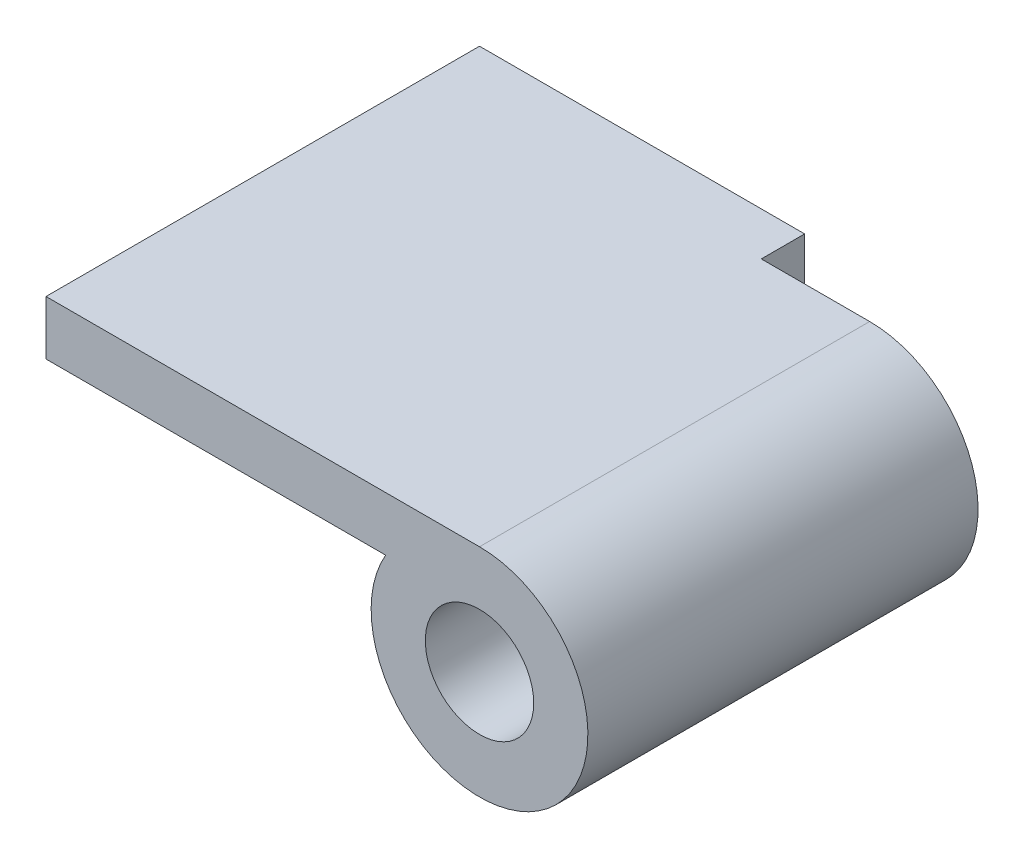
SolidWorks part; units mm, degrees
ref_plane "Front Plane" through (0, 0, 0) normal (0, 0, 1) x (1, 0, 0)
ref_plane "Top Plane" through (0, 0, 0) normal (0, 1, 0) x (1, 0, 0)
ref_plane "Right Plane" through (0, 0, 0) normal (1, 0, 0) x (0, 0, -1)
sketch "Sketch1" plane through (0, 0, 0) normal (0, 0, 1) x (1, 0, 0)
  line L1 (0, 3.175) -> (-25.4, 3.175)
  line L2 (-25.4, 3.175) -> (-25.4, 6.35)
  line L3 (-25.4, 6.35) -> (0, 6.35)
  circle A0 centre (0, 0) radius 6.35
  circle A1 centre (0, 0) radius 3.175
  dimension "D1" = 6.35
  dimension "D2" = 12.7
  dimension "D3" = 25.4
extrude "Boss-Extrude1" add sketch "Sketch1" along normal blind 25.4 contours A0 L3 L2 L1 | A1 A0 region at (-3.0852, 5.3437, 0) region at (-14.613, 4.8143, 0)
sketch "Sketch2" plane through (0, 0, 25.4) normal (0, 0, 1) x (1, 0, 0)
  line L0 (-25.4, 6.35) -> (0, 6.35) construction
  line L1 (6.35, -6.35) -> (-6.35, -6.35)
  line L2 (6.35, -6.35) -> (6.35, 6.35)
  line L3 (6.35, 6.35) -> (-6.35, 6.35)
  line L4 (-6.35, -6.35) -> (-6.35, 6.35)
  line L5 (6.35, -6.35) -> (-6.35, 6.35) construction
  line L6 (6.35, 6.35) -> (-6.35, -6.35) construction
  arc A0 (-5.4993, 3.175) -> (0, 6.35) centre (0, 0) ccw construction
  point P0 (0, 0)
extrude "Cut-Extrude1" cut sketch "Sketch2" along normal blind 2.54 from surface starting at face at (-12.5937, 2.1971, 0)
